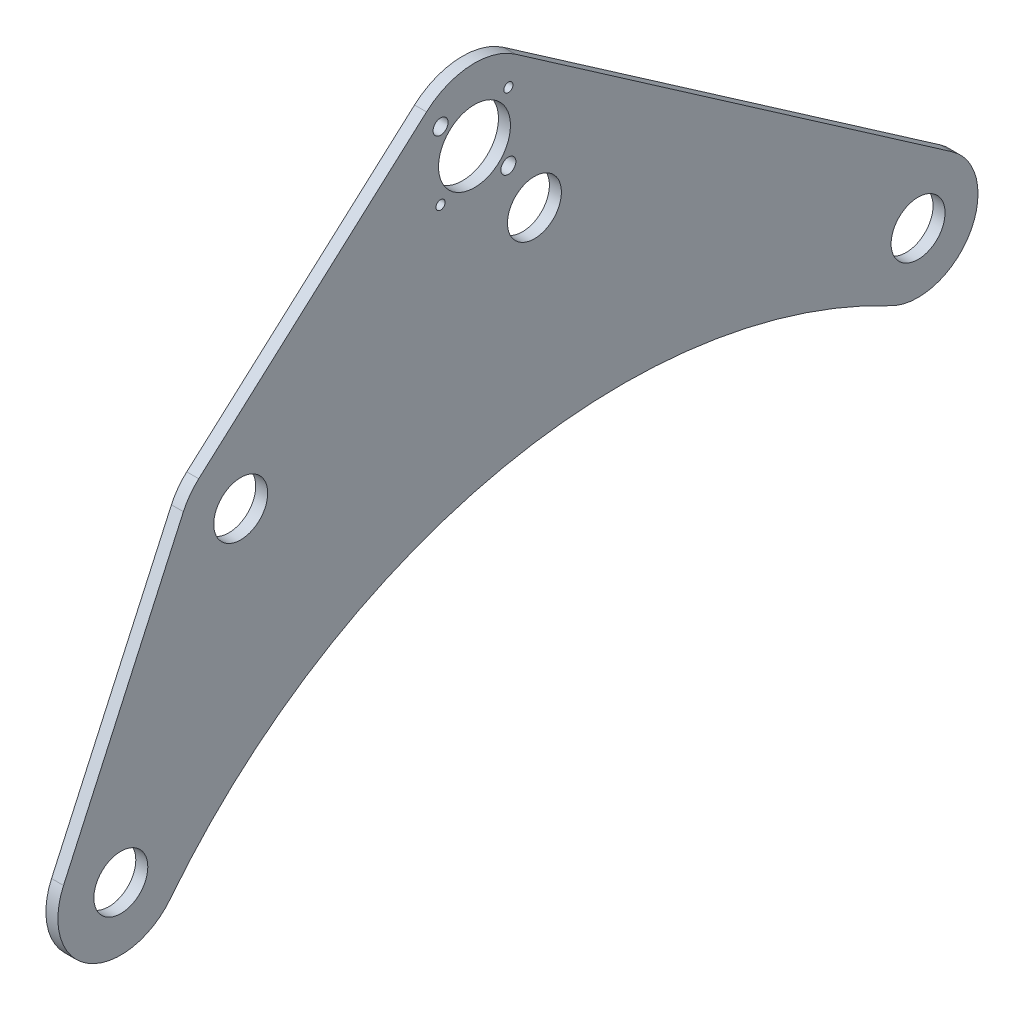
SolidWorks part; units mm, degrees
material "Acrylic (Medium-high impact)"
ref_plane "Front Plane" through (0, 0, 0) normal (0, 0, 1) x (1, 0, 0)
ref_plane "Top Plane" through (0, 0, 0) normal (0, 1, 0) x (1, 0, 0)
ref_plane "Right Plane" through (0, 0, 0) normal (1, 0, 0) x (0, 0, -1)
sketch "Sketch1" plane through (0, 0, 0) normal (1, 0, 0) x (0, 0, -1)
  line L0 (-548.7618, -304.8) -> (152.435, -304.8)
  line L1 (-192.8252, -101.6) -> (-152.4, -101.6)
  line L2 (-234.95, -143.7248) -> (-234.95, -186.4752)
  line L3 (-192.8252, -228.6) -> (-152.4, -228.6)
  line L4 (-152.4, -101.6) -> (-152.4, -228.6)
  circle A1 centre (0, 0) radius 6.35
  circle A6 centre (-422.275, -88.9) radius 9.525
  circle A7 centre (-358.775, 50.8) radius 9.525
  circle A8 centre (-203.2, 111.125) radius 9.525
  arc A9 (-234.95, -186.4752) -> (-192.8252, -228.6) centre (-192.8252, -186.4752) ccw
  arc A10 (-192.8252, -101.6) -> (-234.95, -143.7248) centre (-192.8252, -143.7248) ccw
  circle A11 centre (-358.775, -186.4752) radius 120.65
  circle A12 centre (-234.95, 155.194) radius 29.845
  dimension "D1" = 12.7
  dimension "D2" = 19.05
  dimension "D3" = 42.1248
  dimension "D4" = 127
  dimension "D7" = 203.2
  dimension "D6" = 241.3
  dimension "D16" = 59.69
  dimension "D5" = 82.55
  dimension "D8" = 304.8
  dimension "D9" = 152.4
  dimension "D10" = 422.275
  dimension "D11" = 88.9
  dimension "D12" = 358.775
  dimension "D13" = 50.8
  dimension "D14" = 203.2
  dimension "D15" = 111.125
  dimension "D17" = 234.95
  dimension "D18" = 155.194
sketch "Sketch2" plane through (0, 0, 0) normal (1, 0, 0) x (0, 0, -1)
  line L1 (-452.6243, -75.1048) -> (-389.1243, 64.5952)
  line L3 (-381.0036, 75.6451) -> (-260.3541, 183.5884)
  line L5 (-213.2394, 186.5031) -> (18.0922, 26.0909)
  arc A0 (-381.0036, 75.6451) -> (-389.1243, 64.5952) centre (-358.775, 50.8) ccw
  arc A2 (-452.6243, -75.1048) -> (-396.0719, -109.5104) centre (-422.275, -88.9) ccw
  arc A4 (-213.2394, 186.5031) -> (-260.3541, 183.5884) centre (-234.95, 155.194) ccw
  arc A5 (-14.7643, -28.1083) -> (18.0922, 26.0909) centre (0, 0) ccw
  arc A8 (-396.0719, -109.5104) -> (-14.7643, -28.1083) centre (-156.5012, -297.9484) cw
  circle A12 centre (-422.275, -88.9) radius 9.525 construction
  circle A13 centre (-358.775, 50.8) radius 9.525 construction
  dimension "D1" = 33.3375
  dimension "D2" = 63.5
  dimension "D3" = 76.2
  dimension "D4" = 304.8
extrude "Boss-Extrude1" add sketch "Sketch2" along normal blind 6.35
sketch "Sketch3" plane through (6.35, 0, 0) normal (1, 0, 0) x (0, 0, -1)
  line L0 (-216.9895, 173.1545) -> (-252.9105, 137.2335) construction
  line L1 (-234.95, 155.194) -> (-234.95, 205.0182) construction
  line L2 (-252.9105, 173.1545) -> (-216.9895, 137.2335) construction
  circle A0 centre (-203.2, 111.125) radius 14.2875
  circle A1 centre (-358.775, 50.8) radius 14.2875
  circle A2 centre (-422.275, -88.9) radius 14.2875
  circle A3 centre (-234.95, 155.194) radius 19.05
  circle A4 centre (0, 0) radius 14.2875
  circle A5 centre (-252.9105, 137.2335) radius 2.413
  circle A7 centre (-216.9895, 137.2335) radius 3.9687
  circle A8 centre (-216.9895, 173.1545) radius 2.413
  circle A9 centre (-252.9105, 173.1545) radius 3.9687
  point P18 (-234.95, 155.194)
  point P28 (-234.95, 155.194)
  dimension "D1" = 38.1
  dimension "D2" = 28.575
  dimension "D3" = 4.826
  dimension "D4" = 50.8
  dimension "D5" = 45
  dimension "D6" = 7.9375
  dimension "D7" = 50.8
extrude "Cut-Extrude1" cut sketch "Sketch3" against normal up to next
